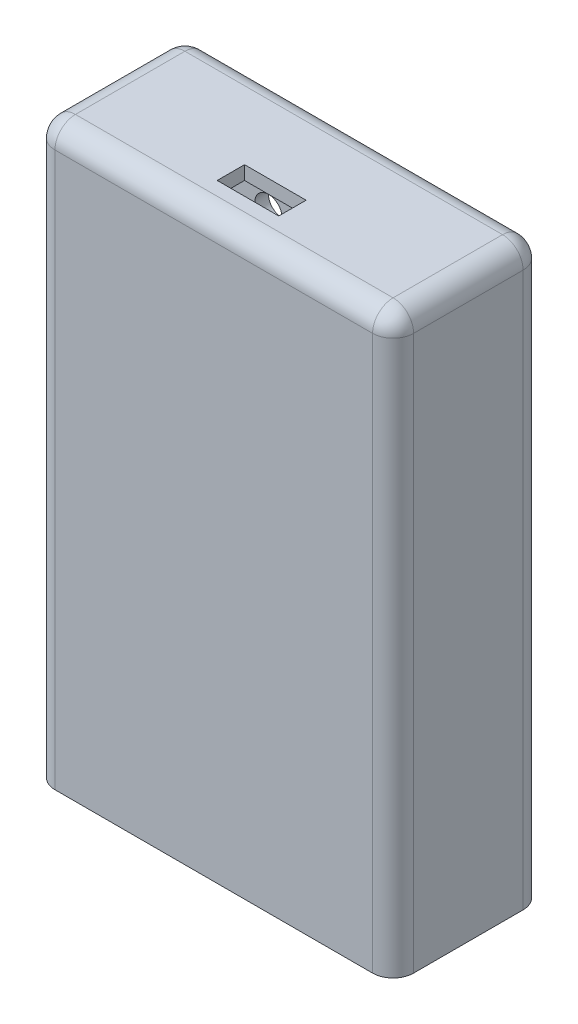
SolidWorks part; units mm, degrees
ref_plane "Front Plane" through (0, 0, 0) normal (0, 0, 1) x (1, 0, 0)
ref_plane "Top Plane" through (0, 0, 0) normal (0, 1, 0) x (1, 0, 0)
ref_plane "Right Plane" through (0, 0, 0) normal (1, 0, 0) x (0, 0, -1)
sketch "Sketch1" plane through (0, 0, 0) normal (0, 1, 0) x (1, 0, 0)
  line L0 (0, 0) -> (0, 67.6823) construction
  line L1 (-10.25, 71.9909) -> (-10.25, -74.1453) construction
  line L2 (0, 0.5742) -> (27.5854, 0.5742) construction
  line L3 (-10.25, 0.5742) -> (-10.25, 1.5742)
  line L4 (-10.25, 1.5742) -> (-9.25, 1.5742)
  line L5 (-9.25, 1.5742) -> (-9.25, 2.5742)
  line L6 (-9.25, 2.5742) -> (-12, 2.5742)
  line L7 (-12, 2.5742) -> (-12, 7.0742)
  line L8 (-12, 7.0742) -> (12, 7.0742)
  line L9 (-10.25, 0.5742) -> (-10.25, -0.4258)
  line L10 (-10.25, -0.4258) -> (-9.25, -0.4258)
  line L11 (-9.25, -0.4258) -> (-9.25, -1.4258)
  line L13 (-9.25, -1.9258) -> (9.25, -1.9258)
  line L14 (9.25, -1.4258) -> (9.25, -1.9258)
  line L15 (13.1095, 8.0742) -> (-13.1095, 8.0742)
  line L16 (-13.1095, 8.0742) -> (-13.1095, 0.5742)
  line L17 (-10.25, -2.9258) -> (10.25, -2.9258)
  line L18 (-9.25, -1.4258) -> (-9.25, -1.9258)
  line L19 (13.1095, 8.0742) -> (13.1095, 0.5742)
  line L21 (9.25, -0.4258) -> (9.25, -1.4258)
  line L22 (10.25, -0.4258) -> (9.25, -0.4258)
  line L23 (10.25, 0.5742) -> (10.25, -0.4258)
  line L24 (12, 2.5742) -> (12, 7.0742)
  line L25 (9.25, 2.5742) -> (12, 2.5742)
  line L26 (9.25, 1.5742) -> (9.25, 2.5742)
  line L27 (10.25, 1.5742) -> (9.25, 1.5742)
  line L28 (10.25, 0.5742) -> (10.25, 1.5742)
  line L29 (-10.25, -2.9258) -> (-13.1095, -2.9258)
  line L30 (-13.1095, -2.9258) -> (-13.1095, 0.5742)
  line L31 (10.25, -2.9258) -> (13.1095, -2.9258)
  line L32 (13.1095, -2.9258) -> (13.1095, 0.5742)
  point P2 (0, -1.9258)
  point P26 (0, -2.9258)
  point P28 (0, 8.0742)
  point P32 (0, 7.0742)
  dimension "D1" = 10.25
  dimension "D2" = 1
  dimension "D3" = 1
  dimension "D4" = 1
  dimension "D5" = 1
  dimension "D6" = 1
  dimension "D7" = 12
  dimension "D9" = 4.5
  dimension "D12" = 1
extrude "Boss-Extrude1" add sketch "Sketch1" along normal blind 20
sketch "Sketch3" plane through (0, 0, 0) normal (0, -1, 0) x (1, 0, 0)
  line L1 (-12, 1.9258) -> (12, 1.9258)
  line L2 (-12, 1.9258) -> (-12, -7.0742)
  line L3 (-12, -7.0742) -> (12, -7.0742)
  line L4 (-13.1095, 2.9258) -> (-13.1095, -8.0742)
  line L5 (-13.1095, -8.0742) -> (13.1095, -8.0742)
  line L6 (13.1095, -8.0742) -> (13.1095, 2.9258)
  line L7 (13.1095, 2.9258) -> (-13.1095, 2.9258)
  line L8 (-13.1095, 2.9258) -> (-13.1095, -8.0742)
  line L9 (-13.1095, -8.0742) -> (13.1095, -8.0742)
  line L10 (13.1095, -8.0742) -> (13.1095, 2.9258)
  line L11 (13.1095, 2.9258) -> (-13.1095, 2.9258)
  line L12 (12, 1.9258) -> (12, -7.0742)
  dimension "D1" = 0
extrude "Boss-Extrude2" add sketch "Sketch3" along normal blind 21
sketch "Sketch4" plane through (0, 20, 0) normal (0, 1, 0) x (1, 0, 0)
  line L4 (-13.1095, 8.0742) -> (-13.1095, -2.9258)
  line L5 (-13.1095, -2.9258) -> (13.1095, -2.9258)
  line L6 (13.1095, -2.9258) -> (13.1095, 8.0742)
  line L7 (13.1095, 8.0742) -> (-13.1095, 8.0742)
  line L8 (-13.1095, 8.0742) -> (-13.1095, -2.9258)
  line L9 (-13.1095, -2.9258) -> (13.1095, -2.9258)
  line L10 (13.1095, -2.9258) -> (13.1095, 8.0742)
  line L11 (13.1095, 8.0742) -> (-13.1095, 8.0742)
  dimension "D1" = 0
extrude "Boss-Extrude3" add sketch "Sketch4" along normal blind 1
sketch "Sketch5" plane through (0, 20, 0) normal (0, -1, 0) x (1, 0, 0)
  line L0 (-10.25, -0.5742) -> (10.25, -0.5742) construction
  line L1 (-10.25, -1.5742) -> (-10.25, 0.4258) construction
  line L2 (10.25, 0.4258) -> (10.25, -1.5742) construction
  line L3 (0, 1.9258) -> (0, -7.0742) construction
  line L4 (-9.25, 1.9258) -> (9.25, 1.9258) construction
  line L5 (12, -7.0742) -> (-12, -7.0742) construction
  line L7 (-2.25, -1.5742) -> (2.25, -1.5742)
  line L8 (-2.25, -1.5742) -> (-2.25, 0.4258)
  line L9 (-2.25, 0.4258) -> (2.25, 0.4258)
  line L10 (2.25, -1.5742) -> (2.25, 0.4258)
  line L11 (-2.25, -1.5742) -> (2.25, 0.4258) construction
  line L12 (-2.25, 0.4258) -> (2.25, -1.5742) construction
  point P12 (0, -0.5742)
  dimension "D1" = 2
  dimension "D2" = 4.5
extrude "Cut-Extrude1" cut sketch "Sketch5" against normal through all
fillet "Fillet1" radius 1.5 8 edges at (13.1095, 0, -8.0742) (12, -0.5, -7.0742) (-12, -0.5, -7.0742) (-13.1095, 0, -8.0742) (13.1095, 0, 2.9258) (12, -10.5, 1.9258) (-13.1095, 0, 2.9258) (-12, -10.5, 1.9258)
fillet "Fillet2" radius 1.5 14 edges at (12, 20, -4.0742) (11.5607, 20, -6.6349) (-12, 20, -4.0742) (-11.5607, 20, -6.6349) (-12.6702, 21, 2.4864) (-13.1095, 21, -2.5742) (-12.6702, 21, -7.6349) (0, 21, -8.0742) (12.6702, 21, -7.6349) (13.1095, 21, -2.5742) (12.6702, 21, 2.4864) (0, 20, 1.9258) (0, 20, -7.0742) (0, 21, 2.9258)
fillet "Fillet3" radius 1.5 6 edges at (9.875, 20, -2.5742) (11.5607, 19.5607, -2.5742) (-9.875, 20, -2.5742) (-11.5607, 19.5607, -2.5742)
sketch "Sketch6" plane through (0, 0, -8.0742) normal (0, 0, -1) x (-1, 0, 0)
  line L0 (0, 19.5) -> (0, -21) construction
  line L1 (11.6095, 19.5) -> (-11.6095, 19.5) construction
  line L2 (11.6095, -21) -> (-11.6095, -21) construction
  line L3 (1.5, 19.5) -> (1.5, -21) construction
  line L4 (3, 19.5) -> (3, -21) construction
  line L5 (4.5, 19.5) -> (4.5, -21) construction
  line L6 (6, 19.5) -> (6, -21) construction
  line L7 (-11.6095, 9.5) -> (11.6095, 9.5) construction
  line L8 (7.5, 19.5) -> (7.5, -21) construction
  line L9 (9, 19.5) -> (9, -21) construction
  line L10 (0, 19.5) -> (0, -21) construction
  line L11 (1.5, 19.5) -> (1.5, -21) construction
  line L12 (3, 19.5) -> (3, -21) construction
  line L13 (4.5, 19.5) -> (4.5, -21) construction
  line L14 (6, 19.5) -> (6, -21) construction
  line L15 (7.5, 19.5) -> (7.5, -21) construction
  line L16 (-1.5, 19.5) -> (-1.5, -21) construction
  line L17 (0, 19.5) -> (0, -21) construction
  line L18 (1.5, 19.5) -> (1.5, -21) construction
  line L19 (3, 19.5) -> (3, -21) construction
  line L20 (4.5, 19.5) -> (4.5, -21) construction
  line L21 (6, 19.5) -> (6, -21) construction
  line L22 (-3, 19.5) -> (-3, -21) construction
  line L23 (-1.5, 19.5) -> (-1.5, -21) construction
  line L24 (0, 19.5) -> (0, -21) construction
  line L25 (1.5, 19.5) -> (1.5, -21) construction
  line L26 (3, 19.5) -> (3, -21) construction
  line L27 (4.5, 19.5) -> (4.5, -21) construction
  line L28 (-4.5, 19.5) -> (-4.5, -21) construction
  line L29 (-3, 19.5) -> (-3, -21) construction
  line L30 (-1.5, 19.5) -> (-1.5, -21) construction
  line L31 (0, 19.5) -> (0, -21) construction
  line L32 (1.5, 19.5) -> (1.5, -21) construction
  line L33 (3, 19.5) -> (3, -21) construction
  line L34 (-6, 19.5) -> (-6, -21) construction
  line L35 (-4.5, 19.5) -> (-4.5, -21) construction
  line L36 (-3, 19.5) -> (-3, -21) construction
  line L37 (-1.5, 19.5) -> (-1.5, -21) construction
  line L38 (0, 19.5) -> (0, -21) construction
  line L39 (1.5, 19.5) -> (1.5, -21) construction
  line L40 (-7.5, 19.5) -> (-7.5, -21) construction
  line L41 (-6, 19.5) -> (-6, -21) construction
  line L42 (-4.5, 19.5) -> (-4.5, -21) construction
  line L43 (-3, 19.5) -> (-3, -21) construction
  line L44 (-1.5, 19.5) -> (-1.5, -21) construction
  line L45 (0, 19.5) -> (0, -21) construction
  line L46 (-1.5, 19.5) -> (-1.5, -21) construction
  line L47 (-3, 19.5) -> (-3, -21) construction
  line L48 (-4.5, 19.5) -> (-4.5, -21) construction
  line L49 (-6, 19.5) -> (-6, -21) construction
  line L50 (-7.5, 19.5) -> (-7.5, -21) construction
  line L51 (-9, 19.5) -> (-9, -21) construction
  line L52 (11.6095, -21) -> (11.6095, 19.5) construction
  line L53 (-11.6095, 19.5) -> (-11.6095, -21) construction
  line L54 (-11.6095, 11.5) -> (11.6095, 11.5) construction
  line L55 (-11.6095, 13.5) -> (11.6095, 13.5) construction
  line L56 (-11.6095, 15.5) -> (11.6095, 15.5) construction
  line L57 (-11.6095, 17.5) -> (11.6095, 17.5) construction
  line L58 (-11.6095, 9.5) -> (11.6095, 9.5) construction
  line L59 (-11.6095, 11.5) -> (11.6095, 11.5) construction
  line L60 (-11.6095, 13.5) -> (11.6095, 13.5) construction
  line L61 (-11.6095, 15.5) -> (11.6095, 15.5) construction
  line L62 (-11.6095, 7.5) -> (11.6095, 7.5) construction
  line L63 (-11.6095, 9.5) -> (11.6095, 9.5) construction
  line L64 (-11.6095, 11.5) -> (11.6095, 11.5) construction
  line L65 (-11.6095, 13.5) -> (11.6095, 13.5) construction
  line L66 (-11.6095, 5.5) -> (11.6095, 5.5) construction
  line L67 (-11.6095, 7.5) -> (11.6095, 7.5) construction
  line L68 (-11.6095, 9.5) -> (11.6095, 9.5) construction
  line L69 (-11.6095, 11.5) -> (11.6095, 11.5) construction
  line L70 (-11.6095, 3.5) -> (11.6095, 3.5) construction
  line L71 (-11.6095, 5.5) -> (11.6095, 5.5) construction
  line L72 (-11.6095, 7.5) -> (11.6095, 7.5) construction
  line L73 (-11.6095, 9.5) -> (11.6095, 9.5) construction
  line L74 (-11.6095, 7.5) -> (11.6095, 7.5) construction
  line L75 (-11.6095, 5.5) -> (11.6095, 5.5) construction
  line L76 (-11.6095, 3.5) -> (11.6095, 3.5) construction
  line L77 (-11.6095, 1.5) -> (11.6095, 1.5) construction
  circle A0 centre (0, 9.5) radius 9 construction
  circle A1 centre (0, 9.5) radius 1
  circle A2 centre (3, 9.5) radius 1
  circle A3 centre (6, 9.5) radius 1
  circle A4 centre (9, 9.5) radius 1
  circle A5 centre (-3, 9.5) radius 1
  circle A6 centre (-6, 9.5) radius 1
  circle A7 centre (-9, 9.5) radius 1
  circle A8 centre (-1.5, 11.5) radius 1
  circle A9 centre (1.5, 11.5) radius 1
  circle A10 centre (4.5, 11.5) radius 1
  circle A11 centre (7.5, 11.5) radius 1
  circle A12 centre (-4.5, 11.5) radius 1
  circle A13 centre (-7.5, 11.5) radius 1
  circle A14 centre (-7.5, 7.5) radius 1
  circle A15 centre (-4.5, 7.5) radius 1
  circle A16 centre (-1.5, 7.5) radius 1
  circle A17 centre (1.5, 7.5) radius 1
  circle A18 centre (4.5, 7.5) radius 1
  circle A19 centre (7.5, 7.5) radius 1
  circle A20 centre (6, 13.5) radius 1
  circle A21 centre (3, 13.5) radius 1
  circle A22 centre (0, 13.5) radius 1
  circle A23 centre (-3, 13.5) radius 1
  circle A24 centre (-6, 13.5) radius 1
  circle A25 centre (-4.5, 15.5) radius 1
  circle A26 centre (-1.5, 15.5) radius 1
  circle A27 centre (1.5, 15.5) radius 1
  circle A28 centre (4.5, 15.5) radius 1
  circle A29 centre (0, 17.5) radius 1
  circle A30 centre (3, 17.5) radius 1
  circle A31 centre (-3, 17.5) radius 1
  circle A32 centre (-6, 5.5) radius 1
  circle A33 centre (-3, 5.5) radius 1
  circle A34 centre (0, 5.5) radius 1
  circle A35 centre (3, 5.5) radius 1
  circle A36 centre (6, 5.5) radius 1
  circle A37 centre (-4.5, 3.5) radius 1
  circle A38 centre (-1.5, 3.5) radius 1
  circle A39 centre (1.5, 3.5) radius 1
  circle A40 centre (4.5, 3.5) radius 1
  circle A41 centre (0, 1.5) radius 1
  circle A42 centre (3, 1.5) radius 1
  circle A43 centre (-3, 1.5) radius 1
  dimension "D2" = 7
  dimension "D6" = 2
  dimension "D1" = 10
  dimension "D3" = 7
  dimension "D4" = 5
  dimension "D5" = 5
extrude "Cut-Extrude2" cut sketch "Sketch6" against normal up to surface (1 mm away) up to face at (0, -1.25, -7.0742)
